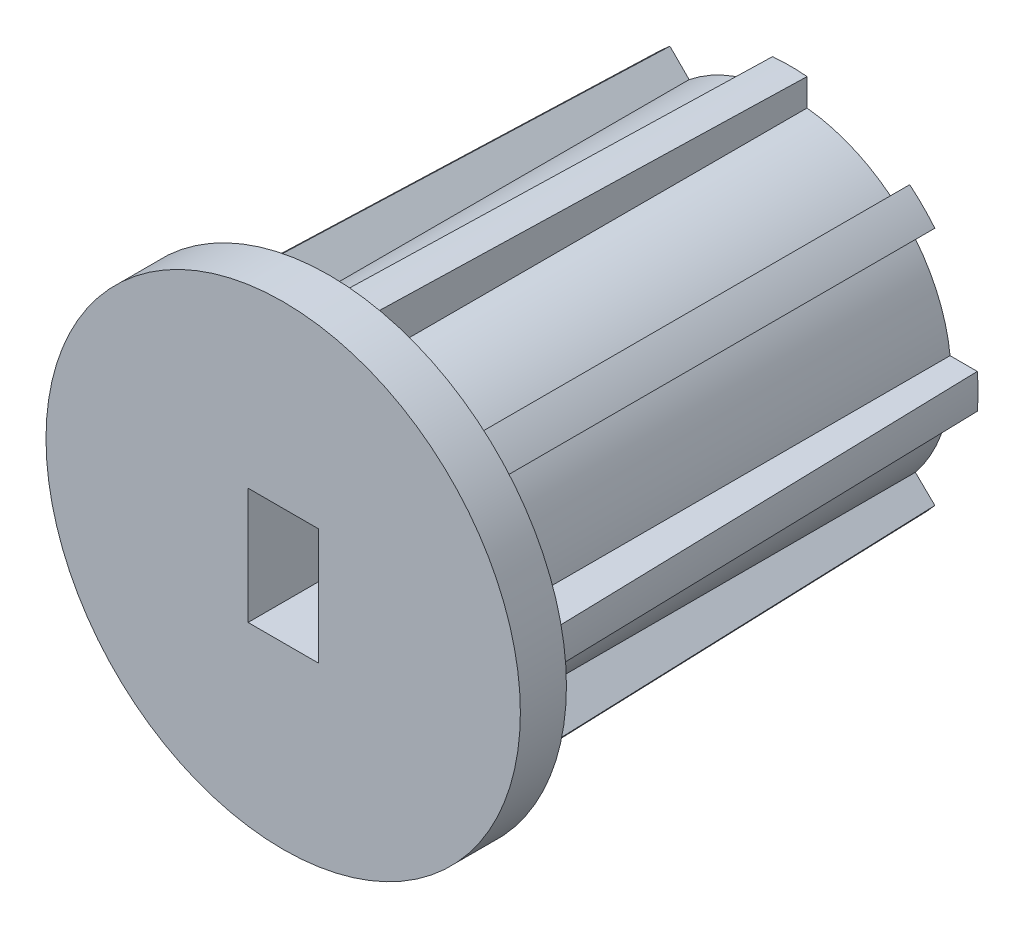
SolidWorks part; units mm, degrees
ref_plane "Спереди" through (0, 0, 0) normal (0, 0, 1) x (1, 0, 0)
ref_plane "Сверху" through (0, 0, 0) normal (0, 1, 0) x (1, 0, 0)
ref_plane "Справа" through (0, 0, 0) normal (1, 0, 0) x (0, 0, -1)
ref_axis "Ось1" through (-88.99, 0, 0) along (1, 0, 0)
ref_axis "Ось2" through (0, 55, 0) along (0, -1, 0)
ref_axis "Ось3" through (0, 0, 55) along (0, 0, -1)
sketch "Эскиз1" plane through (0, 0, 0) normal (0, 0, 1) x (1, 0, 0)
  circle A0 centre (0, 0) radius 20.6
extrude "Бобышка-Вытянуть1" add sketch "Эскиз1" along normal blind 4
sketch "Эскиз2" plane through (0, 0, 0) normal (0, 0, 1) x (1, 0, 0)
  circle A0 centre (0, 0) radius 14
  circle A1 centre (0, 0) radius 10
extrude "Бобышка-Вытянуть2" add sketch "Эскиз2" along normal blind 1 and the other way blind 40 separate body
sketch "Эскиз3" plane through (0, 0, 0) normal (0, 0, -1) x (-1, 0, 0)
  line L0 (-17.3352, 1.5) -> (-13.9194, 1.5)
  line L1 (88.99, 0) -> (-88.99, 0) construction
  line L2 (-1.5, 17.3352) -> (-1.5, 13.9194)
  line L3 (0, 55) -> (0, -55) construction
  line L4 (0, 16.8) -> (0, -16.8) construction
  line L5 (-13.3521, 11.1572) -> (-10.9037, 8.7812)
  line L6 (-11.156, 13.3531) -> (-8.7398, 10.9369)
  line L7 (1.5, 17.3352) -> (1.5, 13.9194)
  line L8 (11.156, 13.3531) -> (8.7398, 10.9369)
  line L9 (13.3521, 11.1572) -> (10.9037, 8.7812)
  line L10 (17.3352, 1.5) -> (13.9194, 1.5)
  line L11 (-21.419, 0) -> (19.2104, 0) construction
  line L12 (17.3352, -1.5) -> (13.9194, -1.5)
  line L13 (13.3521, -11.1572) -> (10.9037, -8.7812)
  line L14 (11.156, -13.3531) -> (8.7398, -10.9369)
  line L15 (1.5, -17.3352) -> (1.5, -13.9194)
  line L16 (-1.5, -17.3352) -> (-1.5, -13.9194)
  line L17 (-11.156, -13.3531) -> (-8.7398, -10.9369)
  line L18 (-13.3521, -11.1572) -> (-10.9037, -8.7812)
  line L19 (-17.3352, -1.5) -> (-13.9194, -1.5)
  arc A0 (-17.3352, -1.5) -> (-17.3352, 1.5) centre (0, 0) cw
  circle A1 centre (0, 0) radius 14 construction
  arc A2 (-13.3521, 11.1572) -> (-11.156, 13.3531) centre (0, 0) cw
  arc A3 (-1.5, 17.3352) -> (1.5, 17.3352) centre (0, 0) cw
  arc A4 (13.3521, 11.1572) -> (11.156, 13.3531) centre (0, 0) ccw
  arc A5 (17.3352, -1.5) -> (17.3352, 1.5) centre (0, 0) ccw
  arc A6 (13.3521, -11.1572) -> (11.156, -13.3531) centre (0, 0) cw
  arc A7 (-1.5, -17.3352) -> (1.5, -17.3352) centre (0, 0) ccw
  arc A8 (-13.3521, -11.1572) -> (-11.156, -13.3531) centre (0, 0) ccw
  circle A9 centre (0, 0) radius 14
  point P45 (-17.4, 0)
  dimension "D2" = 1.5
  dimension "D3" = 17.4
  dimension "D1" = 1.5
extrude "Бобышка-Вытянуть3" add sketch "Эскиз3" along direction (0, 0, 1) on the side of the normal blind 40 contours A9 L18 A8 L17 | A9 L16 A7 L15 | A9 L14 A6 L13 | A9 L12 A5 L10 | A9 L9 A4 L8 | A9 L7 A3 L2 | A9 L6 A2 L5 | A9 L0 A0 L19 region at (15.6758, 0, 0) region at (11.0773, 11.0965, 0) region at (11.0773, -11.0965, 0) region at (0, 15.6758, 0) region at (0, -15.6758, 0) region at (-11.0773, 11.0965, 0) region at (-11.0773, -11.0965, 0) region at (-15.6758, 0, 0)
sketch "Эскиз8" plane through (0, 0, 0) normal (1, 0, 0) x (0, 0, -1)
  line L0 (40, 16.3526) -> (0, 17.4)
  line L3 (40, 17.3352) -> (40, 13.9194) construction
  line L5 (0, 0) -> (46.6699, 0) construction
  line L6 (0, 17.4) -> (40, 17.4)
  line L8 (40, 17.4) -> (40, 16.3526)
  dimension "D1" = 1.5
revolve "Вырез-Повернуть2" cut sketch "Эскиз8" angle 360 about L5
sketch "Эскиз9" plane through (0, 0, 0) normal (0, 0, -1) x (-1, 0, 0)
  circle A0 centre (0, 0) radius 14
extrude "Бобышка-Вытянуть4" add sketch "Эскиз9" along normal blind 14
sketch "Эскиз10" plane through (0, 0, 4) normal (0, 0, 1) x (1, 0, 0)
  line L1 (3.05, 5.05) -> (-3.05, 5.05)
  line L2 (3.05, 5.05) -> (3.05, -5.05)
  line L3 (3.05, -5.05) -> (-3.05, -5.05)
  line L4 (-3.05, 5.05) -> (-3.05, -5.05)
  line L5 (3.05, 5.05) -> (-3.05, -5.05) construction
  line L6 (3.05, -5.05) -> (-3.05, 5.05) construction
  point P0 (0, 0)
  dimension "D1" = 10.1
  dimension "D2" = 6.1
extrude "Вырез-Вытянуть1" cut sketch "Эскиз10" against normal blind 12
scale "Масштаб1" bodies to scale 108 scale about centroid uniform scaling yes scale factor 0.5
